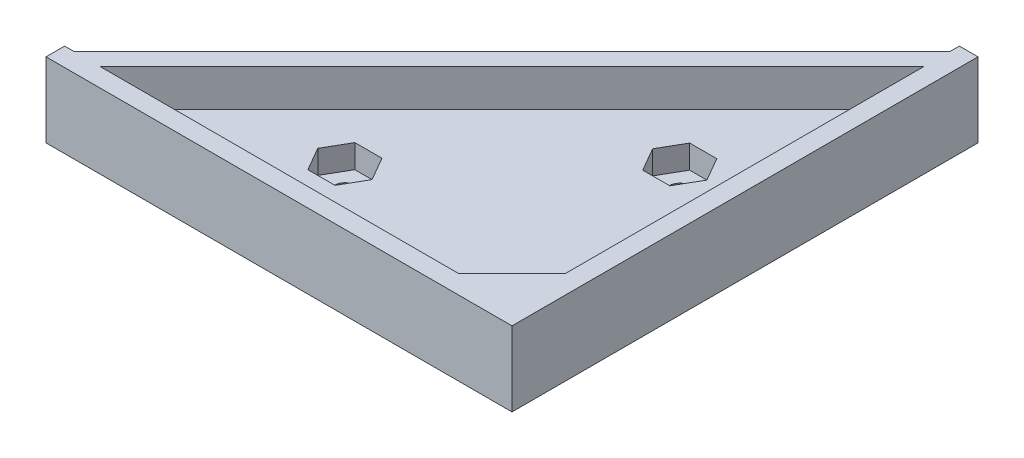
SolidWorks part; units mm, degrees
ref_plane "Front Plane" through (0, 0, 0) normal (0, 0, 1) x (1, 0, 0)
ref_plane "Top Plane" through (0, 0, 0) normal (0, 1, 0) x (1, 0, 0)
ref_plane "Right Plane" through (0, 0, 0) normal (1, 0, 0) x (0, 0, -1)
sketch "Sketch1" plane through (0, 0, 0) normal (0, 1, 0) x (1, 0, 0)
  line L0 (-79.375, 0) -> (0, 0)
  line L1 (0, 0) -> (0, 79.375)
  line L2 (0, 79.375) -> (-3.175, 79.375)
  line L3 (-3.175, 79.375) -> (-3.175, 77.7875)
  line L4 (-3.175, 77.7875) -> (-77.7875, 3.175)
  line L5 (-77.7875, 3.175) -> (-79.375, 3.175)
  line L6 (-79.375, 3.175) -> (-79.375, 0)
  dimension "D1" = 76.2
  dimension "D2" = 79.375
  dimension "D3" = 3.175
  dimension "D4" = 1.5875
extrude "Boss-Extrude1" add sketch "Sketch1" along normal blind 12.7
sketch "Sketch2" plane through (0, 12.7, 0) normal (0, 1, 0) x (1, 0, 0)
  line L0 (-73.2974, 3.175) -> (-12.2411, 3.175)
  line L1 (-3.175, 12.2411) -> (-3.175, 73.2974)
  line L2 (-3.175, 73.2974) -> (-73.2974, 3.175)
  line L3 (-12.2411, 3.175) -> (-3.175, 12.2411)
  line L5 (-79.375, 0) -> (0, 0) construction
  line L6 (0, 0) -> (0, 79.375) construction
  line L7 (-3.175, 77.7875) -> (-77.7875, 3.175) construction
  dimension "D2" = 3.175
  dimension "D3" = 3.175
  dimension "D4" = 3.175
extrude "Cut-Extrude1" cut sketch "Sketch2" against normal blind 6.35
chamfer "Chamfer1" distance 6.35 angle 45 1 edges at (-7.708, 6.35, -7.708)
sketch "Sketch3" plane through (0, 6.35, 0) normal (0, 1, 0) x (1, 0, 0)
  line L0 (-79.375, 0) -> (0, 0) construction
  line L1 (0, 0) -> (0, 79.375) construction
  circle A0 centre (-44.4608, 16.002) radius 1.75
  circle A1 centre (-15.875, 44.45) radius 1.75
  dimension "D1" = 3.5
  dimension "D2" = 3.5
  dimension "D3" = 16.002
  dimension "D4" = 44.4608
  dimension "D5" = 15.875
  dimension "D6" = 44.45
extrude "Cut-Extrude2" cut sketch "Sketch3" against normal blind 6.35
sketch "Sketch4" plane through (0, 6.35, 0) normal (0, 1, 0) x (1, 0, 0)
  line L1 (-13.5656, 40.45) -> (-11.2562, 44.45)
  line L2 (-11.2562, 44.45) -> (-13.5656, 48.45)
  line L3 (-13.5656, 48.45) -> (-18.1844, 48.45)
  line L4 (-18.1844, 48.45) -> (-20.4938, 44.45)
  line L5 (-20.4938, 44.45) -> (-18.1844, 40.45)
  line L6 (-18.1844, 40.45) -> (-13.5656, 40.45)
  line L7 (-39.842, 16.002) -> (-42.1514, 20.002)
  line L8 (-42.1514, 20.002) -> (-46.7702, 20.002)
  line L9 (-46.7702, 20.002) -> (-49.0796, 16.002)
  line L10 (-49.0796, 16.002) -> (-46.7702, 12.002)
  line L11 (-46.7702, 12.002) -> (-42.1514, 12.002)
  line L12 (-42.1514, 12.002) -> (-39.842, 16.002)
  circle A0 centre (-44.4608, 16.002) radius 1.75 construction
  circle A1 centre (-15.875, 44.45) radius 1.75 construction
  circle A2 centre (-44.4608, 16.002) radius 1.75
  circle A3 centre (-15.875, 44.45) radius 1.75
  circle A4 centre (-15.875, 44.45) radius 4 construction
  circle A5 centre (-44.4608, 16.002) radius 4 construction
  dimension "D1" = 8
  dimension "D2" = 8
extrude "Cut-Extrude3" cut sketch "Sketch4" against normal blind 4
